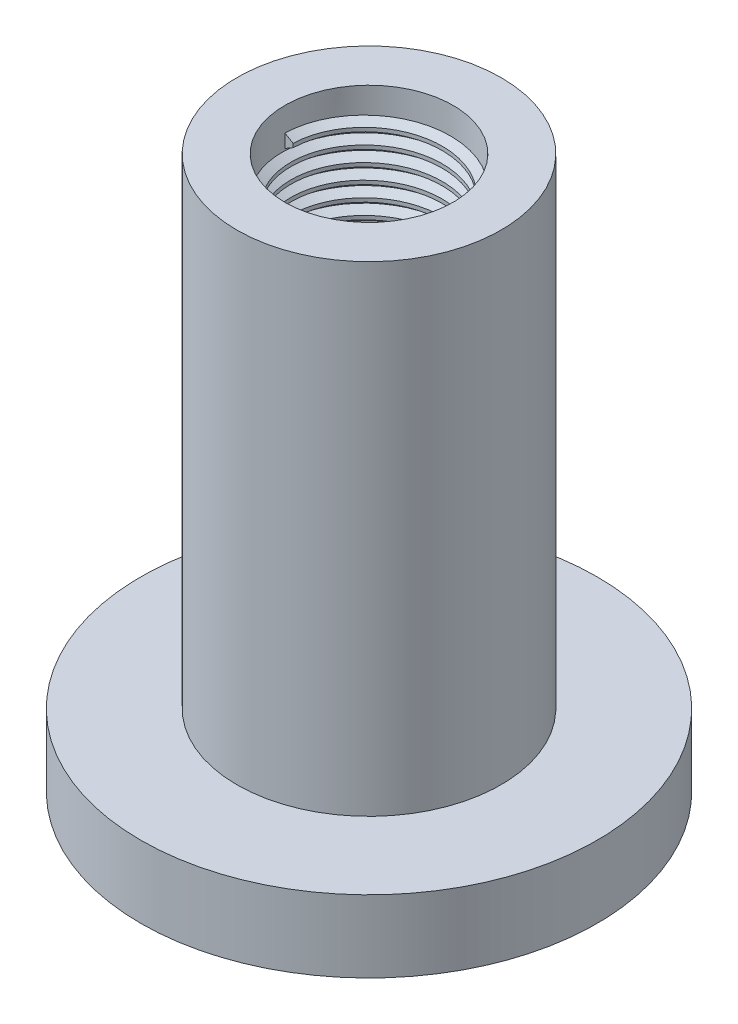
SolidWorks part; units mm, degrees
ref_plane "Front Plane" through (0, 0, 0) normal (0, 0, 1) x (1, 0, 0)
ref_plane "Top Plane" through (0, 0, 0) normal (0, 1, 0) x (1, 0, 0)
ref_plane "Right Plane" through (0, 0, 0) normal (1, 0, 0) x (0, 0, -1)
sketch "Sketch1" plane through (0, 0, 0) normal (0, 1, 0) x (1, 0, 0)
  circle A0 centre (0, 0) radius 4.75
  dimension "D1" = 9.5
extrude "Boss-Extrude1" add sketch "Sketch1" along normal blind 1.5
sketch "Sketch2" plane through (0, 1.5, 0) normal (0, 1, 0) x (1, 0, 0)
  circle A0 centre (0, 0) radius 2.75
  dimension "D1" = 5.5
extrude "Boss-Extrude2" add sketch "Sketch2" along normal blind 10
sketch "Sketch3" plane through (0, 11.5, 0) normal (0, 1, 0) x (1, 0, 0)
  circle A0 centre (0, 0) radius 1.75
  dimension "D1" = 3.5
extrude "Cut-Extrude1" cut sketch "Sketch3" against normal blind 8
thread "Thread2" pitch 0.3175 method extrude profile "Thread Profile2" start angle 0, offset 0.5, length 10, pitch 0.3175, diameter 3.5
ref_plane "Plane2" through (-1.75, 11, 0) normal (0, 0, 1) x (-1, 0, 0)
sketch "Thread Profile2" plane through (-1.75, 11, 0) normal (0, 0, 1) x (-1, 0, 0)
  line L0 (0, 0) -> (0, 0.3175) construction
  line L11 (0, 0) -> (0, 0.2778)
  line L12 (0, 0.2778) -> (-0.1719, 0.1786)
  line L13 (-0.1719, 0.1786) -> (-0.1719, 0.0992)
  line L15 (-0.1719, 0.0992) -> (0, 0)
  line L17 (-0.1719, 0.1389) -> (0, 0.1389) construction
  point P2 (0, 0)
  dimension "Pitch" = 0.3175
  dimension "Profile_Angle" = 60
  dimension "Profile_Land" = 0.0794
  dimension "Profile_Height" = 0.1719
equation "\"mm\"=1"
